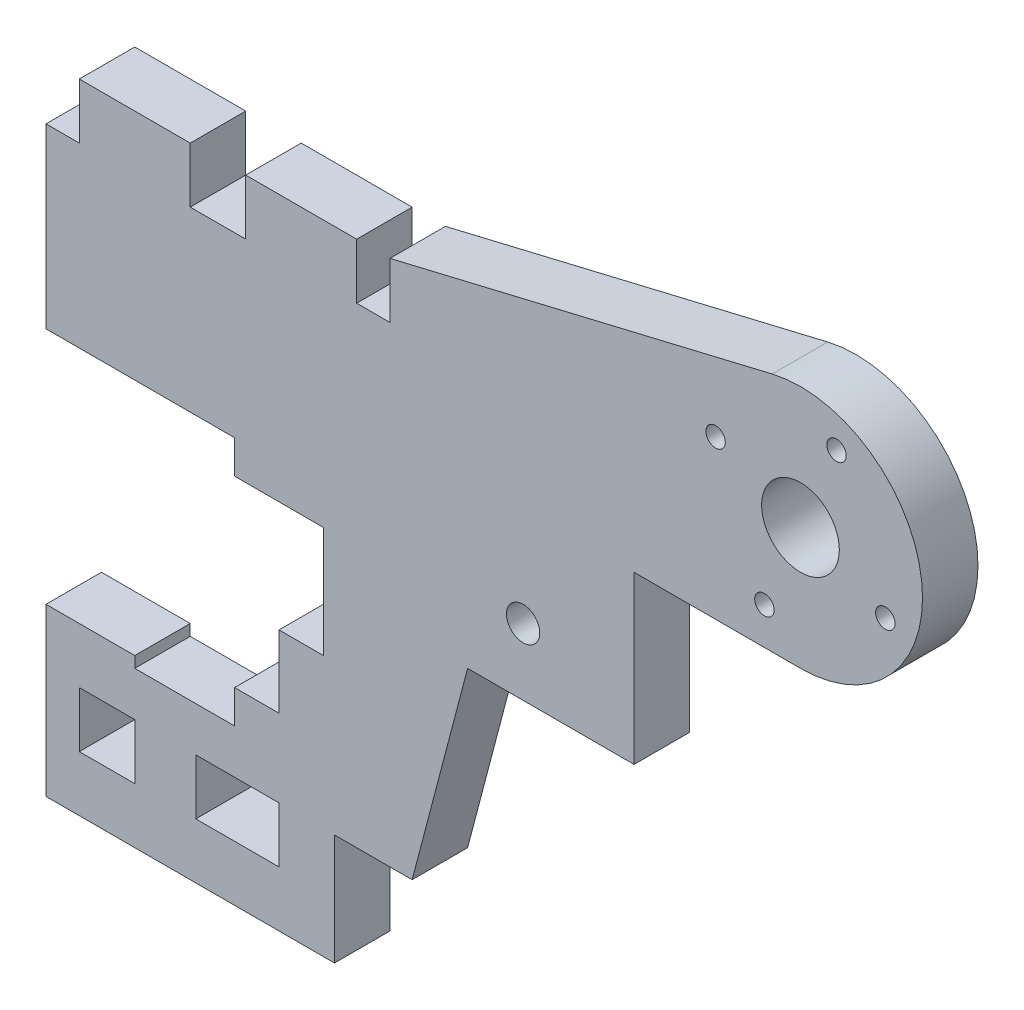
SolidWorks part; units mm, degrees
ref_plane "Plan de face" through (0, 0, 0) normal (0, 0, 1) x (1, 0, 0)
ref_plane "Plan de dessus" through (0, 0, 0) normal (0, 1, 0) x (1, 0, 0)
ref_plane "Plan de droite" through (0, 0, 0) normal (1, 0, 0) x (0, 0, -1)
sketch "Esquisse1" plane through (0, 0, 0) normal (0, 0, 1) x (1, 0, 0)
  line L0 (-8, -10) -> (18, -10)
  line L1 (18, 0) -> (18, -10)
  line L2 (0, 5) -> (0, 4)
  line L3 (5, 42.5) -> (10, 42.5)
  line L4 (56.75, 37.35) -> (63.25, 52.65) construction
  line L5 (20, 42.5) -> (23, 42.5)
  line L6 (-5, 42.5) -> (-5, 47.5)
  line L7 (-5, 47.5) -> (5, 47.5)
  line L8 (5, 42.5) -> (5, 47.5)
  line L9 (18, 0) -> (25, 0)
  line L10 (10, 42.5) -> (10, 47.5)
  line L11 (10, 47.5) -> (20, 47.5)
  line L12 (20, 42.5) -> (20, 47.5)
  line L13 (60, 34) -> (45, 34)
  line L14 (13, 0) -> (5.5, 0)
  line L15 (13, 0) -> (13, -5)
  line L16 (13, -5) -> (5.5, -5)
  line L17 (5.5, 0) -> (5.5, -5)
  line L18 (0, 0) -> (-5, 0)
  line L20 (0, 4) -> (9, 4)
  line L21 (60, 45) -> (52.35, 45) construction
  line L22 (-8, 26.5) -> (9, 26.5)
  line L23 (17, 13.5) -> (17, 23.5)
  line L24 (0, 0) -> (0, -5)
  line L25 (0, 0) -> (0, 5)
  line L26 (0, 5) -> (-8, 5)
  line L27 (-8, -10) -> (-8, 5)
  line L28 (-5, 42.5) -> (-8, 42.5)
  line L29 (0, -5) -> (-5, -5)
  line L31 (-8, 42.5) -> (-8, 26.5)
  line L32 (17, 23.5) -> (9, 23.5)
  line L33 (52.35, 45) -> (52.35, 48.25) construction
  line L34 (9, 7) -> (13, 7)
  line L35 (9, 23.5) -> (9, 26.5)
  line L36 (17, 13.5) -> (13, 13.5)
  line L37 (67.65, 41.75) -> (52.35, 48.25) construction
  line L38 (30, 19) -> (25, 0)
  line L39 (9, 7) -> (9, 4)
  line L40 (-5, 0) -> (-5, -5)
  line L41 (13, 7) -> (13, 13.5)
  line L42 (57.4528, 55.701) -> (23, 47.5)
  line L43 (45, 19) -> (45, 34)
  line L46 (23, 42.5) -> (23, 47.5)
  line L48 (45, 19) -> (30, 19)
  circle A0 centre (35, 25) radius 1.5
  circle A1 centre (60, 45) radius 3.5
  arc A2 (60, 34) -> (57.4528, 55.701) centre (60, 45) ccw
  circle A3 centre (52.35, 45) radius 0.875 construction
  circle A4 centre (52.35, 48.25) radius 0.875
  circle A5 centre (63.25, 52.65) radius 0.875
  circle A6 centre (67.65, 41.75) radius 0.875
  circle A7 centre (56.75, 37.35) radius 0.875
  point P56 (60, 45)
  dimension "D18" = 7
  dimension "D19" = 3
  dimension "D25" = 3.25
  dimension "D27" = 11
  dimension "D28" = 1.75
  dimension "D24" = 7
  dimension "D3" = 10
  dimension "D4" = 5
  dimension "D5" = 5
  dimension "D6" = 8
  dimension "D7" = 15
  dimension "D8" = 10
  dimension "D9" = 16
  dimension "D11" = 3
  dimension "D12" = 4
  dimension "D13" = 10
  dimension "D14" = 3
  dimension "D16" = 8
  dimension "D17" = 8
  dimension "D20" = 20
  dimension "D21" = 2.5
  dimension "D22" = 17
  dimension "D23" = 25
  dimension "D26" = 7.65
  dimension "D30" = 4
  dimension "D31" = 3
  dimension "D32" = 1
  dimension "D34" = 42.5
  dimension "D35" = 26
  dimension "D36" = 5
  dimension "D37" = 5
  dimension "D38" = 7.5
  dimension "D39" = 5
  dimension "D40" = 104.744
  dimension "D41" = 3
  dimension "D42" = 6
  dimension "D43" = 15
  dimension "D29" = 4
extrude "Boss.-Extru.1" add sketch "Esquisse1" along normal blind 5 contours L5 L12 L11 L10 L3 L8 L7 L6 | L28 L31 | L22 L23 L20 L2 L25 L9 | L27 L25 L26 region at (26.047, 29.0944, 0)
